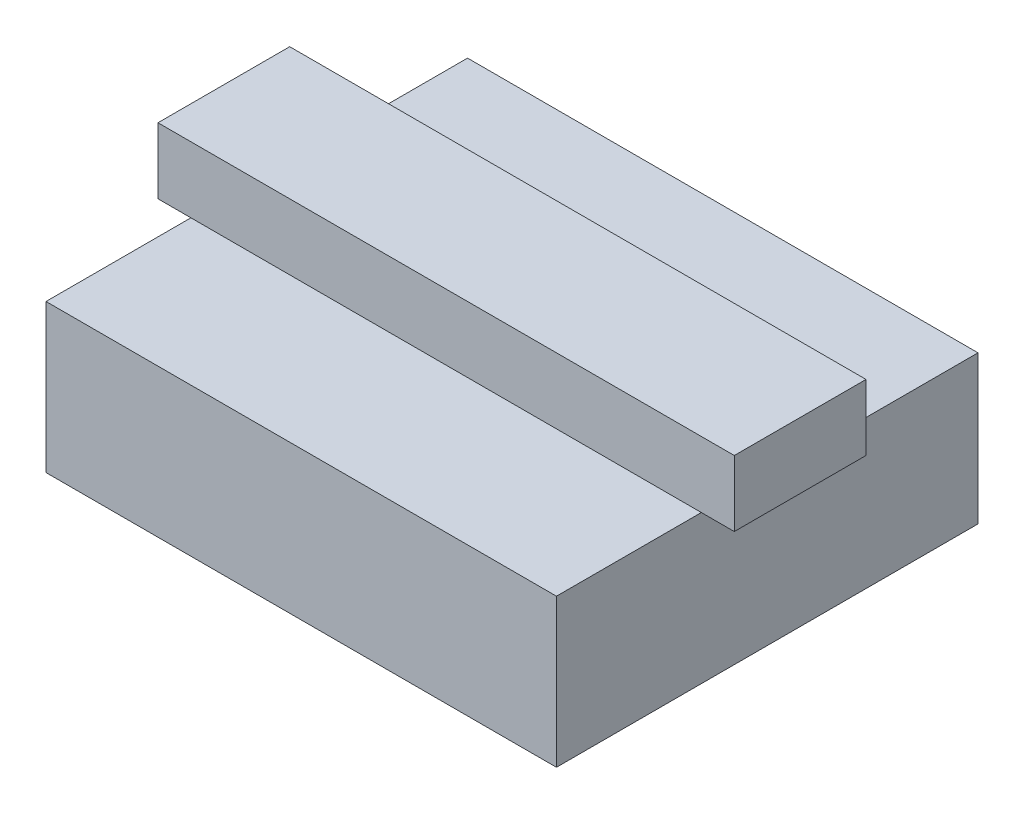
SolidWorks part; units mm, degrees
ref_plane "Front Plane" through (0, 0, 0) normal (0, 0, 1) x (1, 0, 0)
ref_plane "Top Plane" through (0, 0, 0) normal (0, 1, 0) x (1, 0, 0)
ref_plane "Right Plane" through (0, 0, 0) normal (1, 0, 0) x (0, 0, -1)
sketch "Sketch1" plane through (0, 0, 0) normal (0, 1, 0) x (1, 0, 0)
  line L5 (-7.75, -6.4) -> (7.75, -6.4)
  line L6 (-7.75, -6.4) -> (-7.75, 6.4)
  line L7 (-7.75, 6.4) -> (7.75, 6.4)
  line L8 (7.75, -6.4) -> (7.75, 6.4)
  line L9 (-7.75, -6.4) -> (7.75, 6.4) construction
  line L10 (-7.75, 6.4) -> (7.75, -6.4) construction
  point P0 (0, 0)
  dimension "D1" = 15.5
  dimension "D2" = 12.8
extrude "Boss-Extrude1" add sketch "Sketch1" along normal blind 4.5
sketch "Sketch2" plane through (0, 0, 0) normal (0, -1, 0) x (1, 0, 0)
  circle A0 centre (0, 0) radius 1
extrude "Boss-Extrude2" add sketch "Sketch2" along normal blind 4
sketch "Sketch3" plane through (0, 4.5, 0) normal (0, 1, 0) x (1, 0, 0)
  line L0 (-7.75, 6.4) -> (-7.75, -6.4) construction
  line L2 (-7.75, 2) -> (-8.75, 2)
  line L3 (-8.75, 2) -> (-8.75, -2)
  line L4 (-8.75, -2) -> (-7.75, -2)
  line L5 (0, 6.4) -> (0, -6.4) construction
  line L6 (7.75, 6.4) -> (-7.75, 6.4) construction
  line L7 (-7.75, -6.4) -> (7.75, -6.4) construction
  line L8 (8.75, -2) -> (7.75, -2)
  line L9 (8.75, 2) -> (8.75, -2)
  line L10 (7.75, 2) -> (8.75, 2)
  line L11 (-7.75, 2) -> (7.75, 2)
  line L12 (-7.75, -2) -> (7.75, -2)
  dimension "D1" = 1
  dimension "D2" = 4
extrude "Boss-Extrude3" add sketch "Sketch3" along normal blind 2
